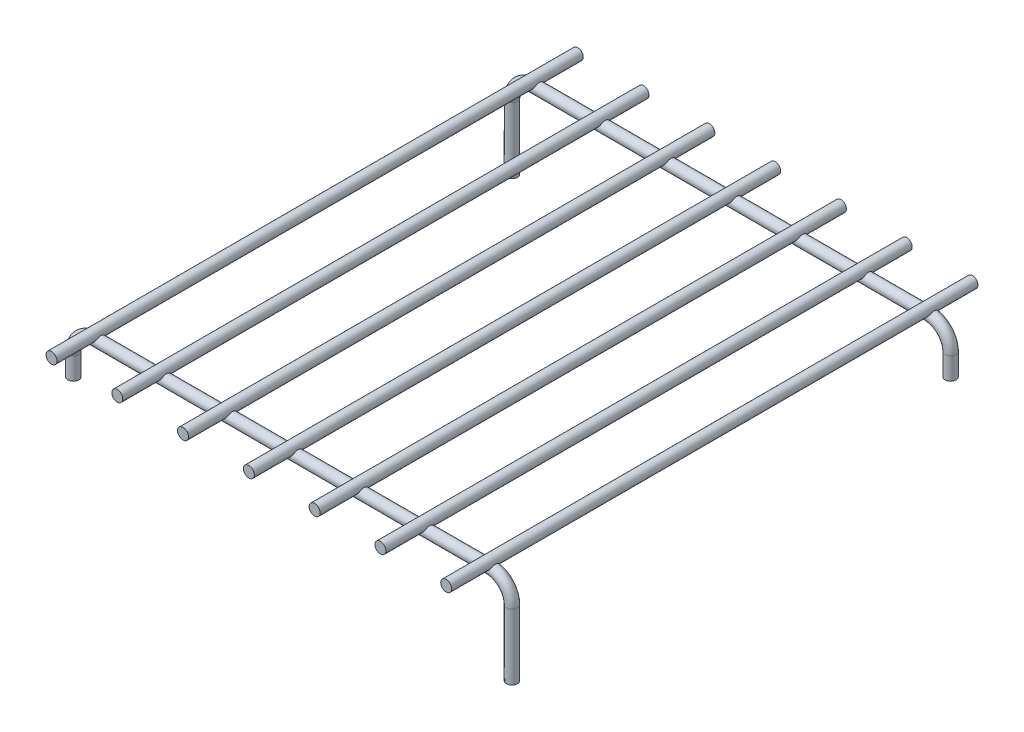
SolidWorks part; units mm, degrees
ref_plane "Front Plane" through (0, 0, 0) normal (0, 0, 1) x (1, 0, 0)
ref_plane "Top Plane" through (0, 0, 0) normal (0, 1, 0) x (1, 0, 0)
ref_plane "Right Plane" through (0, 0, 0) normal (1, 0, 0) x (0, 0, -1)
sketch "Sketch1" plane through (0, 0, 0) normal (0, 0, 1) x (1, 0, 0)
  line L0 (-63.5, -12.7) -> (-63.5, -6.35)
  line L1 (-57.15, 0) -> (57.15, 0)
  line L2 (0, 0) -> (0, 37.1689) construction
  line L3 (63.5, -6.35) -> (63.5, -25.4)
  arc A0 (-63.5, -6.35) -> (-57.15, 0) centre (-57.15, -6.35) cw
  arc A1 (63.5, -6.35) -> (57.15, 0) centre (57.15, -6.35) ccw
  dimension "D1" = 6.35
  dimension "D2" = 127
  dimension "D3" = 12.7
  dimension "D4" = 12.7
ref_plane "Plane1" through (-63.5, -12.7, 0) normal (0, 1, 0) x (-1, 0, 0)
sketch "Sketch2" plane through (-63.5, -12.7, 0) normal (0, 1, 0) x (-1, 0, 0)
  circle A0 centre (0, 0) radius 1.5875
  dimension "D1" = 3.175
sweep "Sweep1" add profiles "Sketch2" path "Sketch1"
ref_axis "Axis1" through (0, 0, -80.9) along (0, 0, 1)
pattern_linear "LPattern1" count 2 spacing 127 along (0, 0, -1) of bodies 101
sketch "Sketch3" plane through (0, 0, 0) normal (0, 0, 1) x (1, 0, 0)
  line L0 (57.15, 1.5875) -> (-57.15, 1.5875) construction
  circle A0 centre (0, 1.5875) radius 1.5875
  dimension "D1" = 3.175
extrude "Extrude1" add sketch "Sketch3" along normal blind 12.7 and the other way blind 139.7 separate body
ref_axis "Axis2" through (-80.9, 0, 0) along (1, 0, 0)
pattern_linear "LPattern2" count 4 spacing 19.05 along (1, 0, 0) count 4 spacing 19.05 along (-1, 0, 0) of bodies 103
combine bodies "Combine1" operation type add bodies to combine 101 102 103 104 105 106 107 108 109
sketch "Sketch4" plane through (0, -12.7, 0) normal (0, -1, 0) x (1, 0, 0)
  circle A1 centre (-63.5, -127) radius 1.5875
  circle A2 centre (-63.5, -127) radius 1.5875
  dimension "D1" = 0
extrude "Extrude2" add sketch "Sketch4" along normal up to surface (12.7 mm away) up to face at (65.0875, -25.4, 0)
sketch "Sketch5" plane through (0, -25.4, 0) normal (0, -1, 0) x (1, 0, 0)
  circle A1 centre (63.5, -127) radius 1.5875
  circle A2 centre (63.5, -127) radius 1.5875
  dimension "D1" = 0
extrude "Cut-Extrude1" cut sketch "Sketch5" against normal up to surface (12.7 mm away) up to face at (-65.0875, -12.7, 0)
